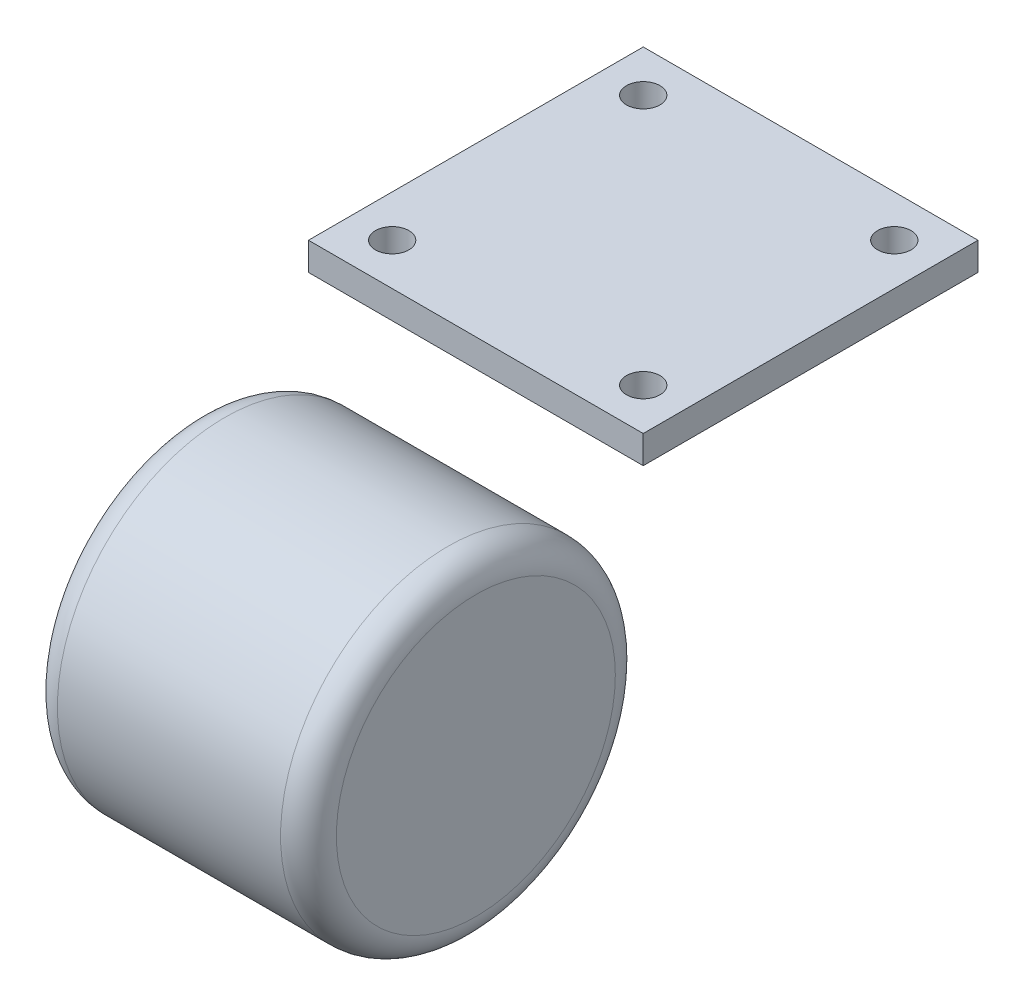
SolidWorks part; units mm, degrees
ref_plane "Front" through (0, 0, 0) normal (0, 0, 1) x (1, 0, 0)
ref_plane "Top" through (0, 0, 0) normal (0, 1, 0) x (1, 0, 0)
ref_plane "Right" through (0, 0, 0) normal (1, 0, 0) x (0, 0, -1)
sketch "Sketch1" plane through (0, 0, 0) normal (0, 1, 0) x (1, 0, 0)
  line L0 (0, 0) -> (0, 52.6463) construction
  line L1 (-30, -30) -> (30, -30)
  line L2 (-30, -30) -> (-30, 30)
  line L3 (-30, 30) -> (30, 30)
  line L4 (30, -30) -> (30, 30)
  line L5 (-30, -30) -> (30, 30) construction
  line L6 (-30, 30) -> (30, -30) construction
  line L7 (0, 0) -> (-64.9392, 0) construction
  line L8 (-26.6814, -85) -> (44.4011, -85) construction
  circle A0 centre (22.5, 22.5) radius 3
  circle A1 centre (-22.5, 22.5) radius 3
  circle A2 centre (22.5, -22.5) radius 3
  circle A3 centre (-22.5, -22.5) radius 3
  point P0 (0, 0)
  dimension "D3" = 6
  dimension "D5" = 45
  dimension "D1" = 60
  dimension "D2" = 60
  dimension "D4" = 115
extrude "Boss-Extrude1" add sketch "Sketch1" along normal blind 5
sketch "Sketch2" plane through (0, 0, 0) normal (1, 0, 0) x (0, 0, -1)
  line L0 (-85, 0) -> (-85, -64.4058) construction
  line L1 (-30, 5) -> (30, 5) construction
  circle A0 centre (-55, -35) radius 30
  point P2 (-55, -46.3143)
  dimension "D1" = 60
  dimension "D2" = 70
extrude "Boss-Extrude2" add sketch "Sketch2" along normal mid plane 50 separate body
fillet "Fillet1" radius 5 2 edges at (-25, -35, 25) (25, -35, 25)
ref_axis "Axis1" through (0, 0, 0) along (0, 1, 0)
